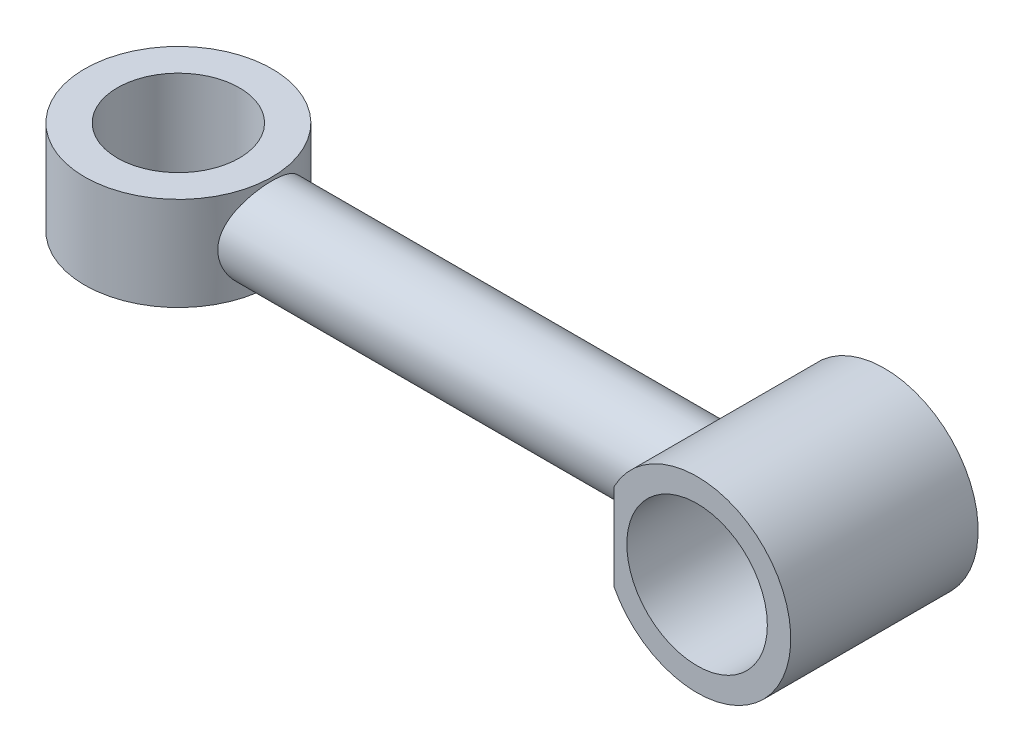
SolidWorks part; units mm, degrees
material "AISI 1010 Steel, hot rolled bar"
ref_plane "Front Plane" through (0, 0, 0) normal (0, 0, 1) x (1, 0, 0)
ref_plane "Top Plane" through (0, 0, 0) normal (0, 1, 0) x (1, 0, 0)
ref_plane "Right Plane" through (0, 0, 0) normal (1, 0, 0) x (0, 0, -1)
sketch "Sketch2" plane through (0, 0, 0) normal (0, 0, 1) x (1, 0, 0)
  circle A0 centre (0, 0) radius 10
  circle A1 centre (0, 0) radius 7.5
  dimension "D1" = 20
  dimension "D2" = 15
extrude "Boss-Extrude1" add sketch "Sketch2" along normal blind 20
sketch "Sketch3" plane through (0, 0, 20) normal (0, 0, 1) x (1, 0, 0)
  line L0 (-8.852, 4.6521) -> (-8.852, -4.6521)
  circle A0 centre (0, 0) radius 10 construction
  arc A1 (-8.852, 4.6521) -> (-8.852, -4.6521) centre (0, 0) ccw
extrude "Cut-Extrude1" cut sketch "Sketch3" against normal blind 20
sketch "Sketch4" plane through (-8.852, 0, 0) normal (-1, 0, 0) x (0, 0, 1)
  circle A0 centre (10, 0) radius 4.6521
extrude "Boss-Extrude2" add sketch "Sketch4" along normal blind 50
sketch "Sketch5" plane through (0, 0, 0) normal (0, 1, 0) x (1, 0, 0)
  circle A0 centre (-65.359, -10) radius 10
  circle A1 centre (-65.359, -10) radius 6.507
  dimension "D1" = 20
  dimension "D2" = 13.014
extrude "Boss-Extrude3" add sketch "Sketch5" along normal blind 5 and the other way blind 5
